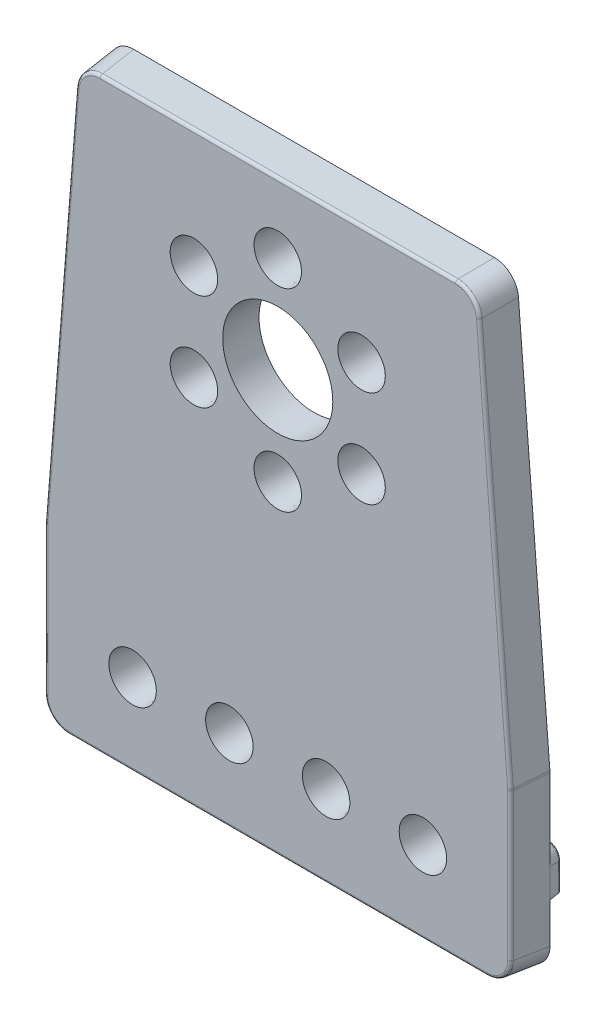
SolidWorks part; units mm, degrees
ref_plane "Front Plane" through (0, 0, 0) normal (0, 0, 1) x (1, 0, 0)
ref_plane "Top Plane" through (0, 0, 0) normal (0, 1, 0) x (1, 0, 0)
ref_plane "Right Plane" through (0, 0, 0) normal (1, 0, 0) x (0, 0, -1)
ref_plane "Plane1" through (0, 0, 0) normal (0, 0, -1) x (-1, 0, 0)
sketch "Sketch1" plane through (0, 0, 0) normal (0, 0, -1) x (-1, 0, 0)
  line L0 (19.5, -20.5) -> (16.75, 14)
  line L1 (16.75, 14) -> (-16.75, 14)
  line L2 (-16.75, 14) -> (-19.5, -20.5)
  line L3 (-19.5, -20.5) -> (-19.5, -35)
  line L4 (-19.5, -35) -> (19.5, -35)
  line L5 (19.5, -35) -> (19.5, -20.5)
extrude "Boss-Extrude1" add sketch "Sketch1" against normal blind 3 draft 5
sketch "Sketch2" plane through (0, 0, 0) normal (0, 0, -1) x (-1, 0, 0)
  line L0 (-19.5, -29.7) -> (-19.5, -26.3)
  line L1 (-19.5, -26.3) -> (19.5, -26.3)
  line L2 (19.5, -26.3) -> (19.5, -29.7)
  line L3 (19.5, -29.7) -> (-19.5, -29.7)
extrude "Boss-Extrude2" add sketch "Sketch2" along normal blind 1 draft 5
ref_plane "Plane2" through (0, -28, 0) normal (0, -1, 0) x (1, 0, 0)
sketch "Sketch3" plane through (0, -28, 0) normal (0, -1, 0) x (1, 0, 0)
  line L0 (-2.0375, 3) -> (-4, 3)
  line L1 (-4, 3) -> (-4, -1)
  line L2 (-4, -1) -> (-2.2125, -1)
  line L3 (-2.2125, -1) -> (-2.3, 0)
  line L4 (-2.3, 0) -> (-2.0375, 3)
  line L5 (-4, 3) -> (-4, -1) construction
revolve "Cut-Revolve1" cut sketch "Sketch3" angle 360 about L5 reverse direction yes
sketch "Sketch4" plane through (0, -28, 0) normal (0, -1, 0) x (1, 0, 0)
  line L0 (-10.0375, 3) -> (-12, 3)
  line L1 (-12, 3) -> (-12, -1)
  line L2 (-12, -1) -> (-10.2125, -1)
  line L3 (-10.2125, -1) -> (-10.3, 0)
  line L4 (-10.3, 0) -> (-10.0375, 3)
  line L5 (-12, 3) -> (-12, -1) construction
revolve "Cut-Revolve2" cut sketch "Sketch4" angle 360 about L5 reverse direction yes
sketch "Sketch5" plane through (0, -28, 0) normal (0, -1, 0) x (1, 0, 0)
  line L0 (5.9625, 3) -> (4, 3)
  line L1 (4, 3) -> (4, -1)
  line L2 (4, -1) -> (5.7875, -1)
  line L3 (5.7875, -1) -> (5.7, 0)
  line L4 (5.7, 0) -> (5.9625, 3)
  line L5 (4, 3) -> (4, -1) construction
revolve "Cut-Revolve3" cut sketch "Sketch5" angle 360 about L5 reverse direction yes
sketch "Sketch6" plane through (0, -28, 0) normal (0, -1, 0) x (1, 0, 0)
  line L0 (13.9625, 3) -> (12, 3)
  line L1 (12, 3) -> (12, -1)
  line L2 (12, -1) -> (13.7875, -1)
  line L3 (13.7875, -1) -> (13.7, 0)
  line L4 (13.7, 0) -> (13.9625, 3)
  line L5 (12, 3) -> (12, -1) construction
revolve "Cut-Revolve4" cut sketch "Sketch6" angle 360 about L5 reverse direction yes
hole_wizard "Hole1" positions "Sketch8" profile "Sketch7" legacy
sketch "Sketch8" plane through (0, 0, 3) normal (0, 0, 1) x (1, 0, 0)
  point P0 (-6.9282, 4)
  point P1 (0, 8)
  point P2 (0, -8)
  point P3 (6.9282, 4)
  point P4 (-6.9282, -4)
  point P5 (6.9282, -4)
sketch "Sketch7" plane through (-6.9282, 4, 3) normal (1, 0, 0) x (0, -1, 0)
  line L0 (0, 0) -> (0, 3)
  line L1 (0, 3) -> (1.7, 3)
  line L2 (1.7, 3) -> (1.9625, 0)
  line L3 (1.9625, 0) -> (0, 0)
  line L4 (0, 110) -> (0, -10) construction
  dimension "Minor Diameter" = 3.4
  dimension "Depth" = 3
  dimension "Major Diameter" = 3.9249
hole_wizard "Ø9.1 (9.1) Diameter Hole1" positions "Sketch10" profile "Sketch9" hole size "Ø9.1" standard "ANSI Metric"
sketch "Sketch10" plane through (0, 0, 3) normal (0, 0, 1) x (1, 0, 0)
  point P0 (0, 0)
sketch "Sketch9" plane through (0, 0, 3) normal (1, 0, 0) x (0, -1, 0)
  line L0 (0, 0) -> (0, 4)
  line L1 (0, 4) -> (4.55, 4)
  line L2 (4.55, 4) -> (4.55, 0)
  line L5 (4.55, 0) -> (0, 0)
  line L11 (0, -6.35) -> (0, 107.95) construction
  dimension "Thru Hole Dia." = 9.1
  dimension "Thru Hole Depth" = 4
fillet "Fillet2" radius 1 1 edges tangent propagation no
fillet "Fillet3" radius 2 6 edges at (19.3688, -20.5052, 1.5) (19.3688, -34.8688, 1.5) (-19.3688, -20.5052, 1.5) (16.6288, 13.8688, 1.5) (-19.3688, -34.8688, 1.5) (-16.6288, 13.8688, 1.5) tangent propagation no
fillet "Fillet4" radius 0.2502 33 edges at (0, -29.6125, -1) (2.2125, -28, -1) (-2.2125, -28, -1) (0, -26.3875, -1) (-16.0919, -29.6125, -1) (-19.4125, -28, -1) (-13.7875, -28, -1) (-16.0919, -26.3875, -1) (16.0919, -29.6125, -1) (19.4125, -28.4981, -1) (19.1212, -26.6788, -1) (13.7875, -28, -1) (15.5938, -26.3875, -1) (-8, -29.6125, -1) (-5.7875, -28, -1) (-8, -26.3875, -1) (-10.2125, -28, -1) (8, -29.6125, -1) (5.7875, -28, -1) (8, -26.3875, -1) (10.2125, -28, -1) (-18.6549, -34.1549, 3) (-19.2375, -26.6674, 3) (0, -34.7375, 3) (-19.236, -20.5105, 3) (18.6549, -34.1549, 3) (-17.9425, -4.264, 3) (19.2375, -26.6674, 3) (-16.0201, 13.2096, 3) (19.236, -20.5105, 3) (0, 13.7375, 3) (17.9425, -4.264, 3) (16.0201, 13.2096, 3) tangent propagation no
